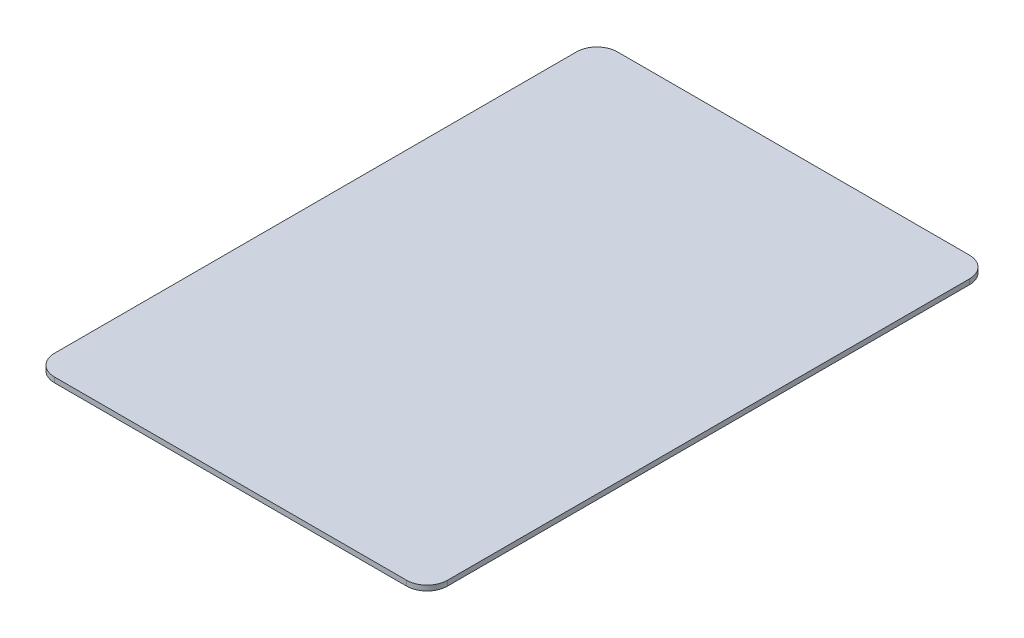
SolidWorks part; units mm, degrees
material "Acrylic (Medium-high impact)"
ref_plane "Front Plane" through (0, 0, 0) normal (0, 0, 1) x (1, 0, 0)
ref_plane "Top Plane" through (0, 0, 0) normal (0, 1, 0) x (1, 0, 0)
ref_plane "Right Plane" through (0, 0, 0) normal (1, 0, 0) x (0, 0, -1)
sketch "Sketch1" plane through (0, 0, 0) normal (0, 1, 0) x (1, 0, 0)
  line L1 (25, -31.5) -> (-25, -31.5)
  line L2 (25, -31.5) -> (25, 31.5)
  line L3 (25, 31.5) -> (-25, 31.5)
  line L4 (-25, -31.5) -> (-25, 31.5)
  line L5 (25, -31.5) -> (-25, 31.5) construction
  line L6 (25, 31.5) -> (-25, -31.5) construction
  line L7 (23, -29.5) -> (-23, -29.5)
  line L8 (23, -29.5) -> (23, 29.5)
  line L9 (23, 29.5) -> (-23, 29.5)
  line L10 (-23, -29.5) -> (-23, 29.5)
  line L11 (23, -29.5) -> (-23, 29.5) construction
  line L12 (23, 29.5) -> (-23, -29.5) construction
  point P0 (0, 0)
  point P6 (0, 0)
  dimension "D1" = 50
  dimension "D2" = 63
  dimension "D3" = 2
  dimension "D4" = 2
sketch "Sketch3" plane through (0, 0, 0) normal (0, 1, 0) x (1, 0, 0)
  line L0 (17.2, -27.5) -> (-17.2, -27.5)
  line L5 (19.2, -25.5) -> (19.2, 25.5)
  line L7 (17.2, 27.5) -> (-17.2, 27.5)
  line L8 (-19.2, -25.5) -> (-19.2, 25.5)
  line L9 (19.2, -27.5) -> (-19.2, 27.5) construction
  line L11 (19.2, 27.5) -> (-19.2, -27.5) construction
  arc A11 (-17.2, -27.5) -> (-19.2, -25.5) centre (-17.2, -25.5) cw
  arc A12 (17.2, -27.5) -> (19.2, -25.5) centre (17.2, -25.5) ccw
  arc A13 (19.2, 25.5) -> (17.2, 27.5) centre (17.2, 25.5) ccw
  arc A14 (-17.2, 27.5) -> (-19.2, 25.5) centre (-17.2, 25.5) ccw
  point P0 (0, 0)
  point P18 (0, 0)
  dimension "D2" = 38.4
  dimension "D1" = 2
  dimension "D3" = 55
extrude "Boss-Extrude1" add sketch "Sketch3" along normal blind 0.5 contours L7 A14 L8 A11 L0 A12 L5 A13 region at (0, 0, 0)
